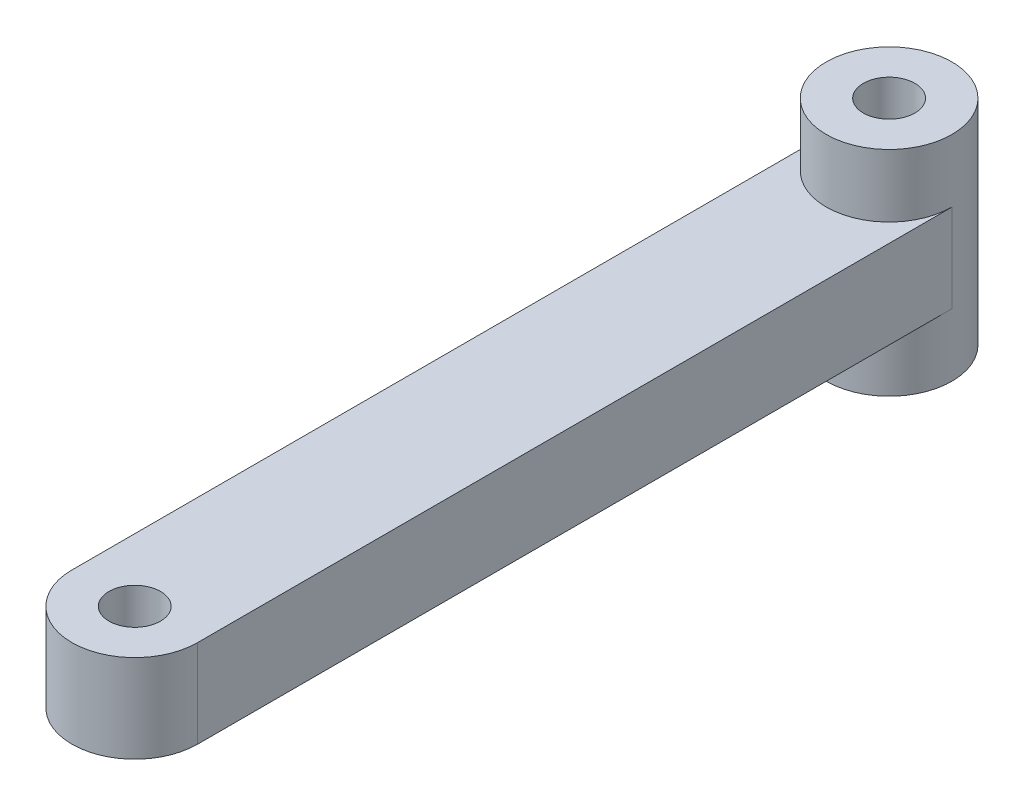
SolidWorks part; units mm, degrees
ref_plane "Plan de face" through (0, 0, 0) normal (0, 0, 1) x (1, 0, 0)
ref_plane "Plan de dessus" through (0, 0, 0) normal (0, 1, 0) x (1, 0, 0)
ref_plane "Plan de droite" through (0, 0, 0) normal (1, 0, 0) x (0, 0, -1)
sketch "Esquisse1" plane through (0, 0, 0) normal (0, 1, 0) x (1, 0, 0)
  line L0 (0, 0) -> (0, 60) construction
  line L1 (-5, 0) -> (-5, 60)
  line L2 (5, 0) -> (5, 60)
  arc A0 (-5, 0) -> (5, 0) centre (0, 0) ccw
  arc A1 (5, 60) -> (-5, 60) centre (0, 60) ccw
  circle A2 centre (0, 60) radius 2.05
  circle A3 centre (0, 0) radius 2.05
  point P3 (0, 30)
  dimension "D3" = 4.1
  dimension "D4" = 4.1
  dimension "D1" = 10
  dimension "D2" = 60
extrude "Boss.-Extru.1" add sketch "Esquisse1" along normal mid plane 7
sketch "Esquisse2" plane through (0, 0, 0) normal (0, 1, 0) x (1, 0, 0)
  line L0 (5, 0) -> (5, 60) construction
  circle A0 centre (0, 60) radius 2.05
  circle A1 centre (0, 60) radius 5
  circle A2 centre (0, 60) radius 2.05 construction
extrude "Boss.-Extru.2" add sketch "Esquisse2" along normal mid plane 17
